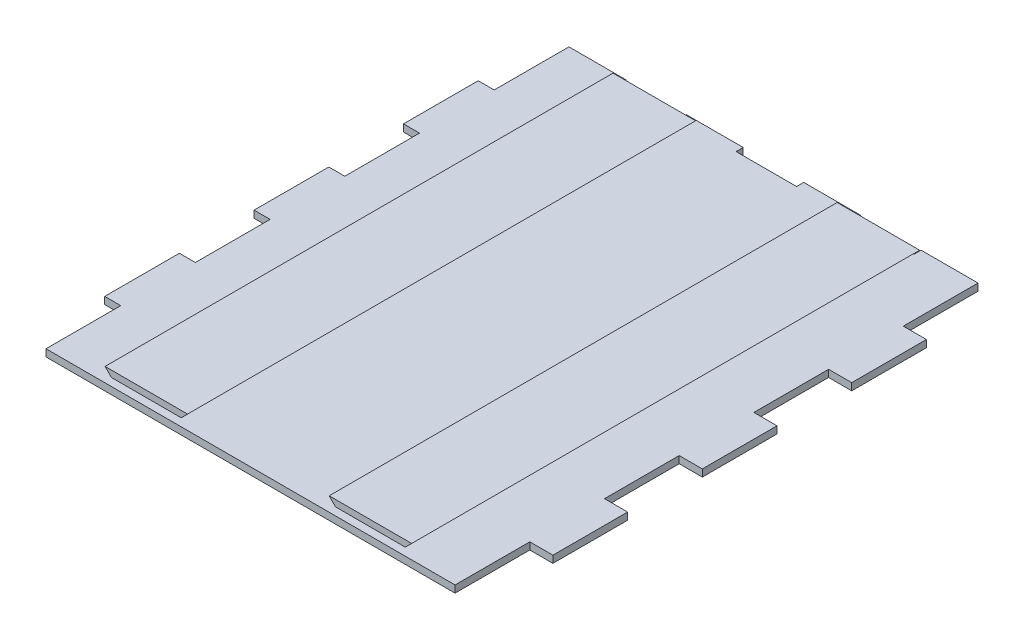
SolidWorks part; units mm, degrees
ref_plane "前视基准面" through (0, 0, 0) normal (0, 0, 1) x (1, 0, 0)
ref_plane "上视基准面" through (0, 0, 0) normal (0, 1, 0) x (1, 0, 0)
ref_plane "右视基准面" through (0, 0, 0) normal (1, 0, 0) x (0, 0, -1)
other "Configuration Table"
sketch "草图4" plane through (0, 0, 0) normal (0, 1, 0) x (1, 0, 0)
  line L6 (-57.5, -72.5) -> (57.5, -72.5)
  line L11 (-57.5, -72.5) -> (-57.5, 72.5)
  line L12 (-57.5, 72.5) -> (57.5, 72.5)
  line L13 (57.5, -72.5) -> (57.5, 72.5)
  line L14 (-57.5, -72.5) -> (57.5, 72.5) construction
  line L15 (-57.5, 72.5) -> (57.5, -72.5) construction
  point P0 (0, 0)
  dimension "D1" = 115
  dimension "D2" = 145
extrude "凸台-拉伸1" add sketch "草图4" along normal blind 2
sketch "草图5" plane through (0, 0, -72.5) normal (0, 0, -1) x (-1, 0, 0)
  line L0 (-57.5, 2) -> (57.5, 2) construction
  line L1 (57.5, 0) -> (41.5, 0)
  line L2 (57.5, 0) -> (57.5, 2)
  line L3 (57.5, 2) -> (41.5, 2)
  line L4 (41.5, 0) -> (41.5, 2)
  line L5 (-57.5, 0) -> (57.5, 0) construction
  line L6 (24.5, 0) -> (8.5, 0)
  line L7 (24.5, 0) -> (24.5, 2)
  line L8 (24.5, 2) -> (8.5, 2)
  line L9 (8.5, 0) -> (8.5, 2)
  line L10 (41.5, 0) -> (24.5, 0)
  line L11 (-8.5, 0) -> (-24.5, 0)
  line L12 (-8.5, 0) -> (-8.5, 2)
  line L13 (-8.5, 2) -> (-24.5, 2)
  line L14 (-24.5, 0) -> (-24.5, 2)
  line L15 (-41.5, 0) -> (-57.5, 0)
  line L16 (-41.5, 0) -> (-41.5, 2)
  line L17 (-41.5, 2) -> (-57.5, 2)
  line L18 (-57.5, 0) -> (-57.5, 2)
  line L19 (8.5, 0) -> (-8.5, 0)
  line L20 (-24.5, 0) -> (-41.5, 0)
  line M17 (-57.5, 0) -> (57.5, 0)
  line M18 (57.5, 0) -> (57.5, 2)
  line M19 (57.5, 2) -> (-57.5, 2)
  line M20 (-57.5, 2) -> (-57.5, 0)
  dimension "D1" = 17
extrude "凸台-拉伸2" add sketch "草图5" along normal blind 2 contours L16 M17 M19 M20 | L14 L12 M17 M19 | L9 L7 M17 M19 | L4 M17 M18 M19 region at (-49.5, 1, -72.5) region at (-16.5, 1, -72.5) region at (16.5, 1, -72.5) region at (49.5, 1, -72.5)
sketch "草图6" plane through (-57.5, 0, 0) normal (-1, 0, 0) x (0, 0, 1)
  line L0 (-74.5, 2) -> (72.5, 2) construction
  line L1 (-53.5, 2) -> (-32.5, 2)
  line L2 (-53.5, 2) -> (-53.5, 0)
  line L3 (-53.5, 0) -> (-32.5, 0)
  line L4 (-32.5, 2) -> (-32.5, 0)
  line L5 (-74.5, 0) -> (72.5, 0) construction
  line L6 (-74.5, 1) -> (-53.5, 1) construction
  line L7 (-11.5, 2) -> (9.5, 2)
  line L8 (-11.5, 2) -> (-11.5, 0)
  line L9 (-11.5, 0) -> (9.5, 0)
  line L10 (9.5, 2) -> (9.5, 0)
  line L11 (30.5, 2) -> (51.5, 2)
  line L12 (30.5, 2) -> (30.5, 0)
  line L13 (30.5, 0) -> (51.5, 0)
  line L14 (51.5, 2) -> (51.5, 0)
  line L15 (-74.5, 0) -> (-74.5, 2) construction
  line L16 (-53.5, 1) -> (-32.5, 1) construction
  line L17 (-32.5, 1) -> (-11.5, 1) construction
  line L18 (-11.5, 1) -> (9.5, 1) construction
  line L19 (9.5, 1) -> (30.5, 1) construction
  line L20 (30.5, 1) -> (51.5, 1) construction
  line L21 (51.5, 1) -> (72.5, 1) construction
  line L22 (72.5, 2) -> (72.5, 0) construction
extrude "凸台-拉伸3" add sketch "草图6" along normal blind 4.5
extrude "凸台-拉伸4" add sketch "草图6<2>" against normal blind 6.5 from surface starting at face at (57.5, 1, -1)
sketch "草图6<2>" plane through (-57.5, 0, 0) normal (-1, 0, 0) x (0, 0, 1) same geometry as "草图6"
sketch "草图7" plane through (0, 2, 0) normal (0, 1, 0) x (1, 0, 0)
  line L0 (0, 0) -> (0, 54.1824) construction
  line L1 (-33, 72.5) -> (-10, 52.5)
  line L2 (-24.5, 72.5) -> (-41.5, 72.5) construction
  line L3 (-10, 52.5) -> (-10, -72.5)
  line L4 (-57.5, -72.5) -> (57.5, -72.5) construction
  line L5 (33, 72.5) -> (10, 52.5)
  line L6 (41.5, 72.5) -> (24.5, 72.5) construction
  line L7 (10, 52.5) -> (10, -72.5)
  line L8 (-10, 52.5) -> (0, 52.5)
  line L9 (0, 52.5) -> (10, 52.5)
  dimension "D1" = 20
  dimension "D2" = 10
sketch "草图8" plane through (0, 0, 72.5) normal (0, 0, 1) x (1, 0, 0)
  line L0 (-41.3, 2) -> (-43.1, 3.8)
  line L1 (-10, 2) -> (0, 2) construction
  line L2 (-57.5, 2) -> (57.5, 2) construction
  line L3 (-21.7, 2) -> (-21.7, 3.8) construction
  line L4 (-19.9, 3.8) -> (-21.7, 2)
  line L5 (0, 2) -> (10, 2) construction
  line L6 (33, 2) -> (10, 2) construction
  line L7 (-41.3, 2) -> (-41.3, 3.8) construction
  line L8 (-43.1, 3.8) -> (-41.3, 3.8)
  line L9 (-41.3, 3.8) -> (-21.7, 3.8)
  line L10 (-21.7, 3.8) -> (-19.9, 3.8)
  line L11 (-41.3, 2) -> (-21.7, 2)
  line L12 (-31.5, 2) -> (-31.5, 3.8) construction
  line L13 (-62, 0) -> (-62, 2) construction
  line L14 (21.7, 2) -> (19.9, 3.8)
  line L15 (41.3, 2) -> (41.3, 3.8) construction
  line L16 (43.1, 3.8) -> (41.3, 2)
  line L17 (21.7, 2) -> (21.7, 3.8) construction
  line L18 (19.9, 3.8) -> (21.7, 3.8)
  line L19 (21.7, 3.8) -> (41.3, 3.8)
  line L20 (41.3, 3.8) -> (43.1, 3.8)
  line L21 (21.7, 2) -> (41.3, 2)
  line L22 (31.5, 2) -> (31.5, 3.8) construction
  line L23 (64, 0) -> (64, 2) construction
  point P19 (-62, 1)
  line M12 (57.5, 2) -> (-57.5, 2)
  dimension "D1" = 1.8
  dimension "D2" = 19.6
  dimension "D3" = 30.5
  dimension "D4" = 19.6
  dimension "D5" = 32.5
extrude "凸台-拉伸5" add sketch "草图8" against normal up to surface (145 mm away) from offset 2.2 contours L10 L9 L8 L0 L4 M12 | L21 L16 L20 L19 L18 L14 region at (-31.5, 2.9252, 72.5) up to face at (33, 1, -72.5) offset against normal yes
